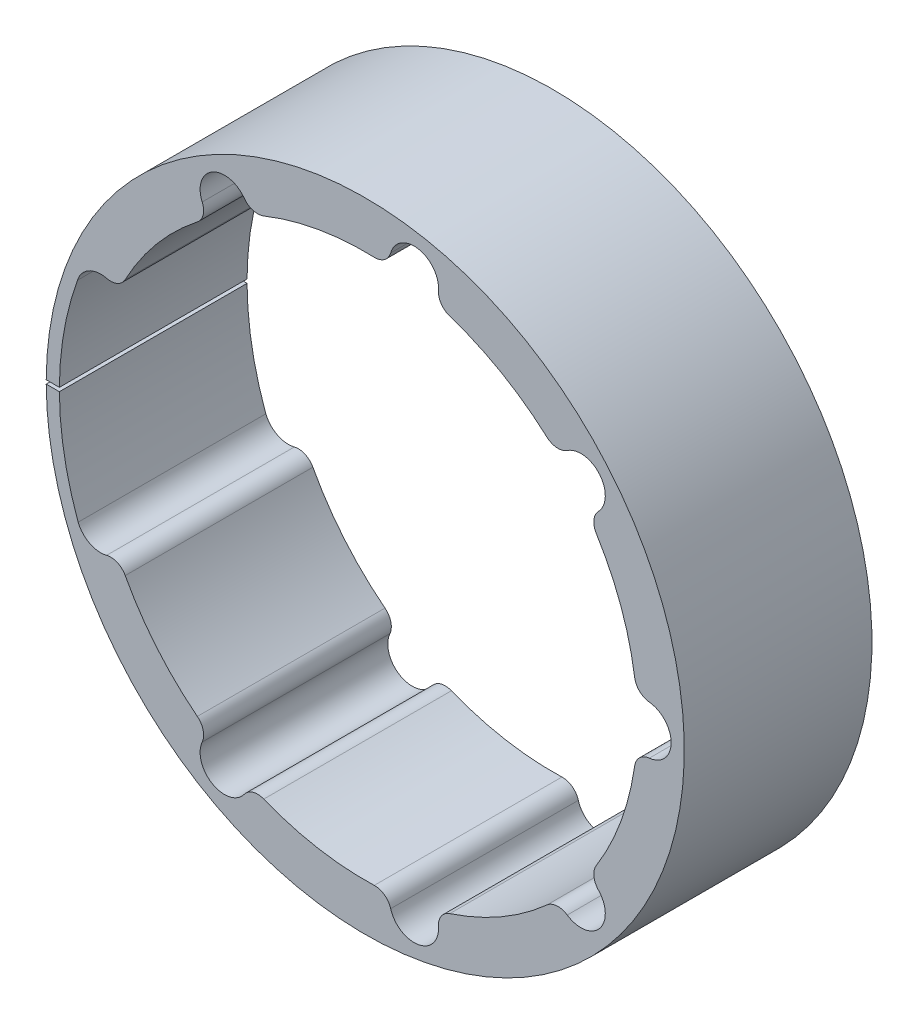
SolidWorks part; units mm, degrees
material "ABS"
ref_plane "Front Plane" through (0, 0, 0) normal (0, 0, 1) x (1, 0, 0)
ref_plane "Top Plane" through (0, 0, 0) normal (0, 1, 0) x (1, 0, 0)
ref_plane "Right Plane" through (0, 0, 0) normal (1, 0, 0) x (0, 0, -1)
sketch "Sketch1" plane through (0, 0, 0) normal (0, 0, 1) x (1, 0, 0)
  line L0 (37.5, 3.25) -> (36.104, 3.25)
  line L1 (37.5, -3.25) -> (36.104, -3.25)
  line L2 (30.8157, -21.6149) -> (29.7463, -20.7176)
  line L3 (26.6376, -26.5942) -> (25.5682, -25.6969)
  line L4 (9.7124, -36.3659) -> (9.47, -34.9912)
  line L5 (3.3112, -37.4946) -> (3.0688, -36.1199)
  line L6 (-15.9354, -34.101) -> (-15.2374, -32.892)
  line L7 (-21.5646, -30.851) -> (-20.8666, -29.642)
  line L8 (-34.1269, -15.8798) -> (-32.8151, -15.4023)
  line L11 (-34.1269, 15.8798) -> (-32.8151, 15.4023)
  line L12 (-21.5646, 30.851) -> (-20.8666, 29.642)
  line L13 (-15.9354, 34.101) -> (-15.2374, 32.892)
  line L14 (3.3112, 37.4946) -> (3.0688, 36.1199)
  line L15 (9.7124, 36.3659) -> (9.47, 34.9912)
  line L16 (26.6376, 26.5942) -> (25.5682, 25.6969)
  line L17 (30.8157, 21.6149) -> (29.7463, 20.7176)
  line L18 (-38.4951, -10.5525) -> (-36.2195, -9.7242) [skipped]
  line L19 (-36.8336, 9.9478) -> (-36.218, 9.7237) [skipped]
  line L20 (0, 0) -> (-3.3956, 0)
  line L21 (-42.5, 0) -> (0, 0)
  line L23 (-42.4993, -0.25) -> (-40.747, -0.25)
  line L25 (-42.4993, 0.25) -> (-40.747, 0.25)
  line L26 (-40.747, -0.25) -> (-40.747, 0.25)
  line L27 (-44.253, -0.25) -> (-40.747, 0.25) construction
  line L28 (-44.253, 0.25) -> (-40.747, -0.25) construction
  arc A0 (36.104, 3.25) -> (29.7463, 20.7176) centre (0, 0) ccw
  arc A1 (37.5, -3.25) -> (37.5, 3.25) centre (37.5, 0) ccw
  circle A10 centre (0, 0) radius 37.5 construction
  arc A11 (26.6376, -26.5942) -> (30.8157, -21.6149) centre (28.7267, -24.1045) ccw
  arc A12 (3.3112, -37.4946) -> (9.7124, -36.3659) centre (6.5118, -36.9303) ccw
  arc A13 (-21.5646, -30.851) -> (-15.9354, -34.101) centre (-18.75, -32.476) ccw
  arc A14 (-38.2468, -14.0556) -> (-34.1269, -15.8798) centre (-35.2385, -12.8258) ccw
  arc A15 (-34.1269, 15.8798) -> (-38.3335, 13.8174) centre (-35.2385, 12.8258) ccw
  arc A16 (-15.9354, 34.101) -> (-21.5646, 30.851) centre (-18.75, 32.476) ccw
  arc A17 (9.7124, 36.3659) -> (3.3112, 37.4946) centre (6.5118, 36.9303) ccw
  arc A18 (30.8157, 21.6149) -> (26.6376, 26.5942) centre (28.7267, 24.1045) ccw
  arc A19 (25.5682, 25.6969) -> (9.47, 34.9912) centre (0, 0) ccw
  arc A20 (3.0688, 36.1199) -> (-15.2374, 32.892) centre (0, 0) ccw
  arc A21 (-20.8666, 29.642) -> (-32.8151, 15.4023) centre (0, 0) ccw
  arc A23 (-32.8151, -15.4023) -> (-20.8666, -29.642) centre (0, 0) ccw
  arc A24 (-15.2374, -32.892) -> (3.0688, -36.1199) centre (0, 0) ccw
  arc A25 (9.47, -34.9912) -> (25.5682, -25.6969) centre (0, 0) ccw
  arc A26 (29.7463, -20.7176) -> (36.104, -3.25) centre (0, 0) ccw
  circle A27 centre (0, 0) radius 42.5
  arc A28 (-38.3335, 13.8174) -> (-38.2468, -14.0556) centre (0, 0) ccw
  point P24 (0, 0)
  point P53 (0, 0)
  point P70 (0, 0)
  dimension "D1" = 72.5
  dimension "D2" = 6.5
  dimension "D4" = 75
  dimension "D5" = 85
  dimension "D3" = 9
  dimension "D6" = 0.5
extrude "Boss-Extrude1" add sketch "Sketch1" along normal blind 25 contours A28 A15 L11 A21 L12 A16 L13 A20 L14 A17 L15 A19 L16 A18 L17 A0 L0 A1 L1 A26 L2 A11 L3 A25 L4 A12 L5 A24 L6 A13 L7 A23 L8 A14 L23 A27 L25 region at (36.802, 4.4521, 0)
fillet "Fillet1" radius 2.2 16 edges at (-32.8151, -15.4023, 12.5) (-20.8666, -29.642, 12.5) (-15.2374, -32.892, 12.5) (3.0688, -36.1199, 12.5) (9.47, -34.9912, 12.5) (25.5682, -25.6969, 12.5) (29.7463, -20.7176, 12.5) (36.104, -3.25, 12.5) (36.104, 3.25, 12.5) (29.7463, 20.7176, 12.5) (25.5682, 25.6969, 12.5) (9.47, 34.9912, 12.5) (3.0688, 36.1199, 12.5) (-15.2374, 32.892, 12.5) (-20.8666, 29.642, 12.5) (-32.8151, 15.4023, 12.5)
